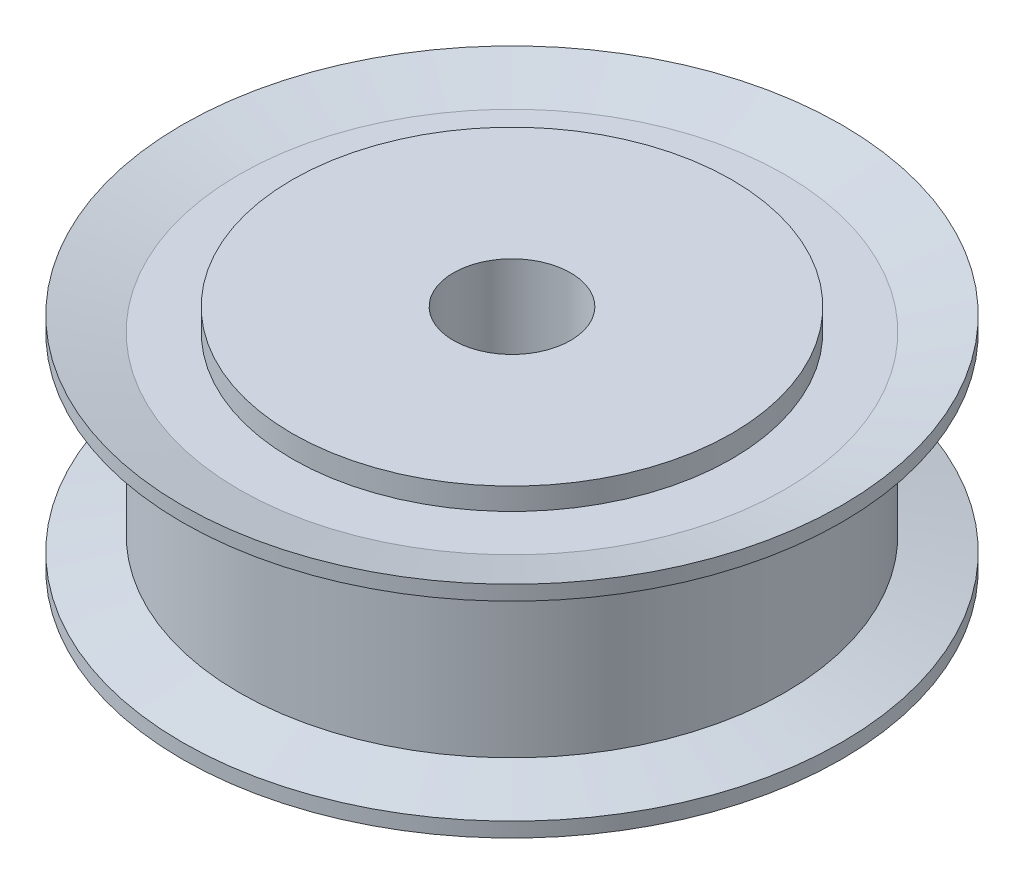
SolidWorks part; units mm, degrees
material "6061 合金"
ref_plane "前基準面" through (0, 0, 0) normal (0, 0, 1) x (1, 0, 0)
ref_plane "上基準面" through (0, 0, 0) normal (0, 1, 0) x (1, 0, 0)
ref_plane "右基準面" through (0, 0, 0) normal (1, 0, 0) x (0, 0, -1)
sketch "草圖1" plane through (0, 0, 0) normal (0, 0, 1) x (1, 0, 0)
  line L0 (0, 49.34) -> (0, -26.8952) construction
  line L1 (18.62, 0) -> (6.3419, 0) construction
  line L3 (4, -8) -> (4, 8)
  line L5 (18.62, 5.5) -> (15, 5.5)
  line L6 (15, 8) -> (15, 5.5)
  line L8 (19.1, 5.5) -> (19.1, -5.5) construction
  line L9 (18.62, -5.5) -> (18.62, 5.5)
  line L10 (15, -5.5) -> (18.62, -5.5)
  line L11 (15, 8) -> (4, 8)
  line L12 (15, -8) -> (15, -5.5)
  line L20 (15, -8) -> (4, -8)
  dimension "D2" = 8
  dimension "D3" = 37.24
  dimension "D6" = 11
  dimension "D7" = 30
  dimension "D8" = 16
  dimension "D9" = 11
  dimension "D12" = 38.2
  dimension "D15" = 3.62
revolve "旋轉1" add sketch "草圖1" angle 360 about L0
sketch "草圖7" plane through (0, 0, 0) normal (0, 0, 1) x (1, 0, 0)
  line L0 (0, 0) -> (0, 8) construction
  line L1 (15, 8) -> (-15, 8) construction
  line L3 (-18.62, -5.5) -> (18.62, -5.5) construction
  line L5 (-15, -5.5) -> (-15, -8) construction
  line L8 (0, 0) -> (-16, 0) construction
  line L12 (-22.5, -6.5) -> (-18.62, -5.5)
  line L13 (-22.5, -7.5) -> (-22.5, -6.5)
  line L14 (-22.5, -7.5) -> (-18.62, -6.5)
  line L15 (-15, -5.5) -> (-15, -6.5)
  line L16 (-18.62, -6.5) -> (-15, -6.5)
  line L17 (-18.62, -5.5) -> (-15, -5.5)
  dimension "D1" = 45
  dimension "D2" = 1
  dimension "D3" = 1
revolve "旋轉2" add sketch "草圖7" angle 360 about L0
mirror "鏡射1" about plane through (0, 0, 0) normal (0, 1, 0) of "旋轉2"
ref_plane "平面1" through (0, 0, 18.62) normal (0, 0, 1) x (1, 0, 0)
ref_axis "基準軸1" through (0, -8, 0) along (0, 1, 0)
